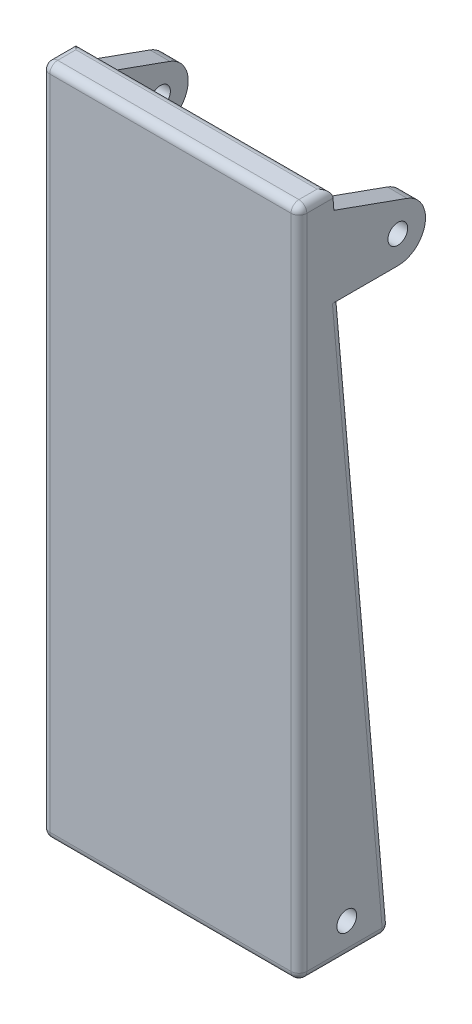
SolidWorks part; units mm, degrees
ref_plane "Front Plane" through (0, 0, 0) normal (0, 0, 1) x (1, 0, 0)
ref_plane "Top Plane" through (0, 0, 0) normal (0, 1, 0) x (1, 0, 0)
ref_plane "Right Plane" through (0, 0, 0) normal (1, 0, 0) x (0, 0, -1)
sketch "Sketch1" plane through (0, 0, 0) normal (0, 0, 1) x (1, 0, 0)
  line L0 (0, 0) -> (0, 170)
  line L1 (0, 0) -> (65, 0)
  line L3 (0, 170) -> (65, 170)
  line L5 (32.5, -96.9231) -> (32.5, 96.9231) construction
  line L6 (65, 0) -> (65, 170)
  point P9 (32.5, 0)
  dimension "D1" = 170
  dimension "D2" = 65
  dimension "D3" = 65
extrude "Boss-Extrude1" add sketch "Sketch1" along normal blind 35
sketch "Sketch4" plane through (65, 0, 0) normal (1, 0, 0) x (0, 0, -1)
  line L1 (-35, 0) -> (0, 0) construction
  line L2 (0, 0) -> (0, 170) construction
  line L3 (-35, 170) -> (0, 170) construction
  line L4 (-7.6378, 158.5894) -> (-26.1646, 165.231)
  line L5 (-26.1646, 165.231) -> (-26.5513, 170)
  line L6 (-10, 145) -> (-24.5239, 145)
  line L7 (-24.5239, 145) -> (-11.7789, 0)
  line L9 (-11.7789, 0) -> (-35, 0)
  line L10 (-35, 0) -> (-35, 170)
  line L11 (-35, 170) -> (-26.5513, 170)
  circle A1 centre (-10, 152) radius 7
  line M2 (0, 0) -> (0, 170)
  line M3 (0, 170) -> (-35, 170)
  line M5 (-35, 0) -> (0, 0)
  dimension "D4" = 14
  dimension "D5" = 10
  dimension "D6" = 18
extrude "Cut-Extrude6" cut sketch "Sketch4" against normal through all contours A1 L6 L7 L4 M5 M2 M3 region at (65, 89.2622, 9.46)
sketch "Sketch5" plane through (65, 0, 0) normal (1, 0, 0) x (0, 0, -1)
  circle A0 centre (-10, 152) radius 2.5
  dimension "D1" = 5
extrude "Cut-Extrude7" cut sketch "Sketch5" against normal through all
sketch "Sketch6" plane through (65, 0, 0) normal (1, 0, 0) x (0, 0, -1)
  line L0 (-12.9121, 12.477) -> (-12.9121, 0) construction
  line L1 (-35, 0) -> (-11.7789, 0) construction
  circle A0 centre (-22.9121, 8) radius 2.5
  dimension "D1" = 5
  dimension "D2" = 10
  dimension "D3" = 8
extrude "Cut-Extrude8" cut sketch "Sketch6" against normal through all
sketch "Sketch7" plane through (0, -1.0274, 11.6886) normal (0, 0.0876, -0.9962) x (-1, 0, 0)
  line L0 (-65, 145.2918) -> (0, 145.2918) construction
  line L1 (-32.5, 145.2918) -> (-32.5, 13.5564)
  line L2 (0, 13.5564) -> (-65, 13.5564) construction
  point P0 (-32.5, 145.2918)
ref_plane "Plane3" through (32.5, 0, 0) normal (1, 0, 0) x (0, -0.9962, -0.0876)
sketch "Sketch8" plane through (32.5, 0, 0) normal (1, 0, 0) x (0, -0.9962, -0.0876)
  line L0 (-167.8983, 23.9169) -> (-34.1398, 23.9169)
  line L1 (-34.1398, 23.9169) -> (-34.1398, -11.7336)
  line L2 (-145.2918, -11.7336) -> (-13.5564, -11.7336) construction
  line L3 (-34.1398, -11.7336) -> (-169.2796, -11.5804)
  line L4 (-166.8873, -11.5966) -> (-171.6719, -11.5643) construction
  line L5 (-169.2796, -11.5804) -> (-169.2796, 23.9169)
  line L6 (-169.2796, 23.9169) -> (-167.8983, 23.9169)
extrude "Cut-Extrude9" cut sketch "Sketch8" against normal blind 27.5 and the other way blind 27.5
ref_plane "Plane2" through (27.5, 0, 0) normal (1, 0, 0) x (0, 0, -1)
ref_plane "Plane1" through (27.5, 0, 0) normal (1, 0, 0) x (0, 0, -1)
ref_plane "Plane4" through (32.5, 0, 0) normal (1, 0, 0) x (0, 0, -1)
sketch "Sketch9" plane through (32.5, 0, 0) normal (1, 0, 0) x (0, 0, -1)
  line L1 (-31.5176, 31.6696) -> (-6.7431, 31.6696)
  line L2 (-31.5176, 31.6696) -> (-31.5176, 0)
  line L3 (-31.5176, 0) -> (-6.7431, 0)
  line L4 (-6.7431, 31.6696) -> (-6.7431, 0)
extrude "Cut-Extrude13" cut sketch "Sketch9" against normal blind 25 and the other way blind 25
fillet "Fillet1" radius 2 9 edges at (65, 170, 30.7757) (0, 170, 30.7757) (32.5, 170, 26.5513) (32.5, 170, 35) (0, 72.5, 18.1514) (65, 72.5, 18.1514) (32.5, 0, 35) (0, 85, 35) (65, 85, 35)
fillet "Fillet2" radius 2 8 edges at (0.5858, 0.5858, 34.4142) (0, 0, 23.3933) (0.5858, 0, 12.3669) (64.4142, 0.5858, 34.4142) (65, 0, 23.3933) (64.4142, 0, 12.3669) (4.75, 0, 11.7789) (60.25, 0, 11.7789)
